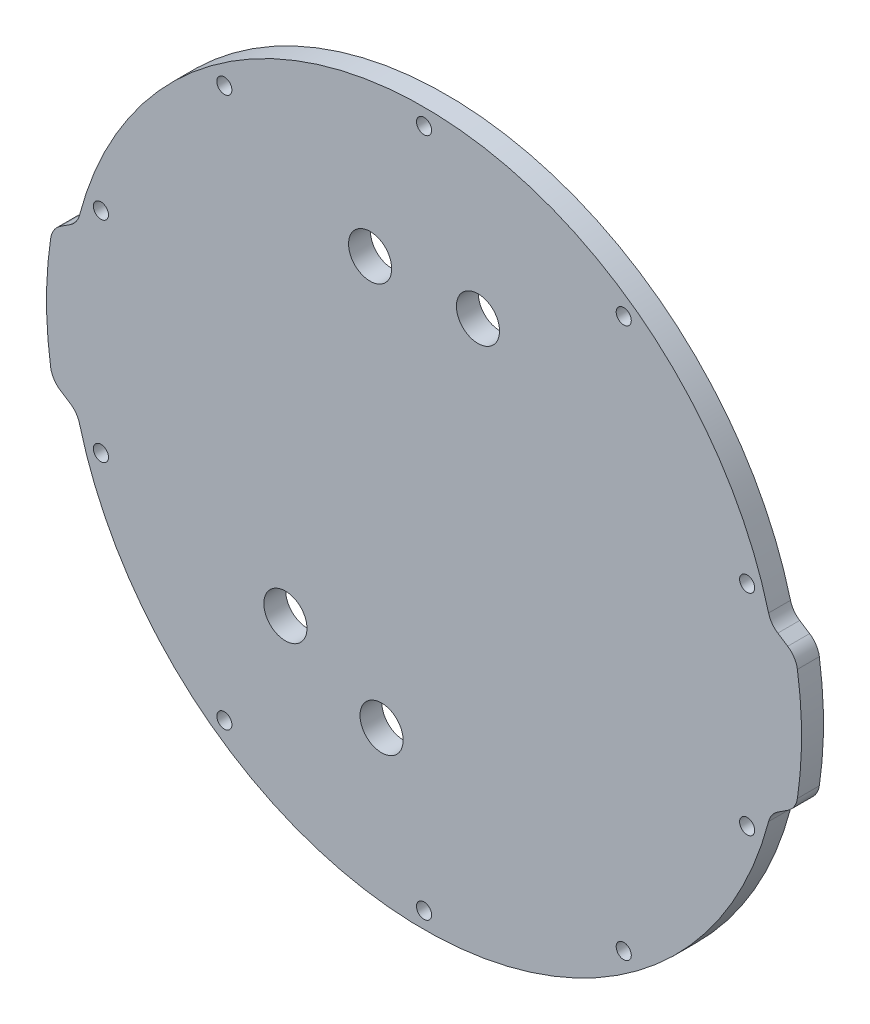
SolidWorks part; units mm, degrees
material "6061 Alloy"
ref_plane "Front Plane" through (0, 0, 0) normal (0, 0, 1) x (1, 0, 0)
ref_plane "Top Plane" through (0, 0, 0) normal (0, 1, 0) x (1, 0, 0)
ref_plane "Right Plane" through (0, 0, 0) normal (1, 0, 0) x (0, 0, -1)
sketch "Sketch1" plane through (0, 0, 0) normal (0, 0, 1) x (1, 0, 0)
  line L0 (-87.5, 0) -> (87.5, 0) construction
  line L1 (0, -87.5) -> (0, 87.5) construction
  line L2 (-86.1626, 15.24) -> (-80.3219, 19.05)
  line L3 (86.1626, 15.24) -> (80.3219, 19.05)
  line L4 (-86.1626, -15.24) -> (-80.3219, -19.05)
  line L5 (86.1626, -15.24) -> (80.3219, -19.05)
  line L6 (-44.5, 30.3438) -> (-43.5, 30.3438) construction
  line L7 (-43.5, -19.6562) -> (43.5, -19.6562) construction
  line L8 (-43.5, -19.6562) -> (-43.5, 30.3438) construction
  line L9 (-43.5, 30.3438) -> (43.5, 30.3438) construction
  line L10 (43.5, -19.6562) -> (43.5, 30.3438) construction
  line L11 (-43.5, -19.6562) -> (43.5, 30.3438) construction
  line L12 (-43.5, 30.3438) -> (43.5, -19.6562) construction
  line L13 (-44.5, 31.3438) -> (44.5, 31.3438) construction
  line L14 (-44.5, 31.3438) -> (-44.5, -20.6562) construction
  line L15 (-44.5, -20.6562) -> (44.5, -20.6562) construction
  line L16 (44.5, 31.3438) -> (44.5, -20.6562) construction
  line L17 (-43.5, 30.3438) -> (-43.5, 31.3438) construction
  line L18 (43.5, -19.6562) -> (43.5, -20.6562) construction
  line L20 (44.5, -19.6562) -> (43.5, -19.6562) construction
  arc A0 (-86.1626, 15.24) -> (-86.1626, -15.24) centre (0, 0) ccw
  arc A1 (-80.3219, 19.05) -> (-80.3219, -19.05) centre (0, 0) ccw construction
  circle A2 centre (0, 0) radius 78.74 construction
  circle A5 centre (0, 78.74) radius 1.75
  circle A10 centre (46.2822, 63.702) radius 1.75
  circle A11 centre (74.8862, 24.332) radius 1.75
  circle A12 centre (74.8862, -24.332) radius 1.75
  circle A13 centre (46.2822, -63.702) radius 1.75
  circle A14 centre (0, -78.74) radius 1.75
  circle A15 centre (-46.2822, -63.702) radius 1.75
  circle A16 centre (-74.8862, -24.332) radius 1.75
  circle A17 centre (-74.8862, 24.332) radius 1.75
  circle A18 centre (-46.2822, 63.702) radius 1.75
  arc A19 (86.1626, 15.24) -> (-86.1626, 15.24) centre (0, 0) ccw construction
  arc A20 (86.1626, -15.24) -> (86.1626, 15.24) centre (0, 0) ccw
  arc A21 (-86.1626, -15.24) -> (86.1626, -15.24) centre (0, 0) ccw construction
  arc A22 (80.3219, 19.05) -> (-80.3219, 19.05) centre (0, 0) ccw
  arc A23 (80.3219, -19.05) -> (80.3219, 19.05) centre (0, 0) ccw construction
  arc A24 (-80.3219, -19.05) -> (80.3219, -19.05) centre (0, 0) ccw
  circle A26 centre (-12.5, 46.3438) radius 10 construction
  circle A27 centre (12.5, 46.3438) radius 10 construction
  circle A31 centre (0, 0) radius 63 construction
  circle A32 centre (-12.5, 46.3438) radius 15 construction
  circle A33 centre (-9.846, -46.9793) radius 10 construction
  circle A34 centre (-32.1347, -35.6562) radius 10 construction
  circle A35 centre (-9.846, -46.9793) radius 15 construction
  circle A36 centre (-32.1347, -35.6562) radius 15 construction
  circle A38 centre (-32.1347, -35.6562) radius 5
  circle A39 centre (-9.846, -46.9793) radius 5
  circle A40 centre (-12.5, 46.3438) radius 5
  circle A41 centre (12.5, 46.3438) radius 5
  point P0 (0, 5.3438)
  dimension "D2" = 157.48
  dimension "D3" = 165.1
  dimension "D4" = 175
  dimension "D5" = 3.5
  dimension "D6" = 50
  dimension "D7" = 87
  dimension "D12" = 20
  dimension "D13" = 126
  dimension "D14" = 5
  dimension "D17" = 10
  dimension "D9" = 19.05
  dimension "D10" = 15.24
  dimension "D11" = 1
  dimension "D8" = 10
extrude "Boss-Extrude1" add sketch "Sketch1" along normal mid plane 5.08
fillet "Fillet1" radius 5.08 8 edges at (-86.1626, 15.24, 0) (-80.3219, 19.05, 0) (-86.1626, -15.24, 0) (-80.3219, -19.05, 0) (86.1626, -15.24, 0) (80.3219, -19.05, 0) (86.1626, 15.24, 0) (80.3219, 19.05, 0)
